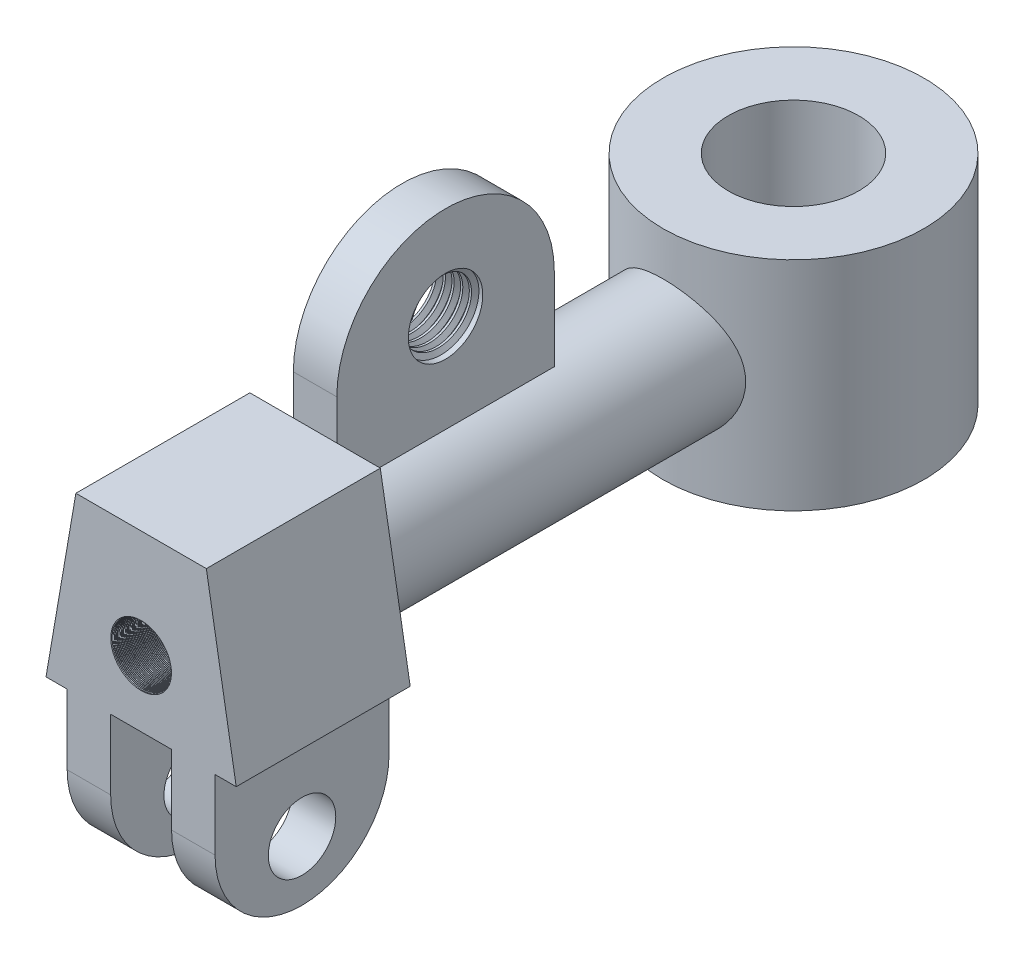
SolidWorks part; units mm, degrees
ref_plane "Front Plane" through (0, 0, 0) normal (0, 0, 1) x (1, 0, 0)
ref_plane "Top Plane" through (0, 0, 0) normal (0, 1, 0) x (1, 0, 0)
ref_plane "Right Plane" through (0, 0, 0) normal (1, 0, 0) x (0, 0, -1)
sketch "Sketch1" plane through (0, 0, 0) normal (0, 1, 0) x (1, 0, 0)
  line L0 (0, 0) -> (0, 27608.447) construction
  line L1 (0, 0) -> (-27608.447, 0) construction
  circle A0 centre (0, 0) radius 15
  circle A1 centre (0, 0) radius 30
  dimension "D1" = 30
  dimension "D2" = 60
extrude "Boss-Extrude1" add sketch "Sketch1" along normal mid plane 50
ref_plane "Plane1" through (0, 0, 130) normal (0, 0, 1) x (1, 0, 0)
sketch "Sketch2" plane through (0, 0, 130) normal (0, 0, 1) x (1, 0, 0)
  line L0 (-21.868, -15.1886) -> (21.868, -15.1886)
  line L1 (21.868, -15.1886) -> (15, 24.8114)
  line L2 (15, 24.8114) -> (-15, 24.8114)
  line L3 (-15, 24.8114) -> (-21.868, -15.1886)
  circle A0 centre (0, 0) radius 6.9775
  point P5 (0, 24.8114)
  point P8 (0, 0)
  point P9 (0, -15.1886)
  point P10 (0, 0)
  point P11 (0, 0)
  point P12 (0, 0)
  dimension "D1" = 43.736
  dimension "D2" = 40
  dimension "D3" = 30
extrude "Boss-Extrude2" add sketch "Sketch2" against normal blind 20 and the other way blind 20 separate body
sketch "Sketch3" plane through (0, 0, 110) normal (0, 0, -1) x (-1, 0, 0)
  circle A0 centre (0, 0) radius 6.9775 construction
  circle A1 centre (0, 0) radius 6.9775
  circle A2 centre (0, 0) radius 15
  dimension " 30" = 30
extrude "Boss-Extrude3" add sketch "Sketch3" along normal up to next
ref_plane "Plane2" through (22, 0, 0) normal (1, 0, 0) x (0, 0, -1)
sketch "Sketch8" plane through (22, 0, 0) normal (1, 0, 0) x (0, 0, -1)
  line L0 (-150, -15.1886) -> (-150, -51.2498)
  line L1 (-150, -51.2498) -> (-110, -51.2498)
  line L2 (-110, -51.2498) -> (-110, -15.1886)
  line L3 (-110, -15.1886) -> (-150, -15.1886)
extrude "Boss-Extrude4" add sketch "Sketch8" against normal blind 10 from offset 5 offset against normal yes
sketch "Sketch9" plane through (17, 0, 0) normal (1, 0, 0) x (0, 0, -1)
  circle A0 centre (-130, -37.4946) radius 7.7568
extrude "Cut-Extrude1" cut sketch "Sketch9" against normal blind 10
fillet "Fillet1" 2 edges at (12, -51.2498, 150) (12, -51.2498, 110) type full round first side face at (6, -14.2039, 150) second side face at (-15, 0, 110) middle face at (12, -51.2498, 130)
mirror "Mirror1" about plane through (0, 0, 0) normal (1, 0, 0) of "Cut-Extrude1", "Boss-Extrude4", "Fillet1"
ref_plane "Plane3" through (0, 15, 0) normal (0, 1, 0) x (1, 0, 0)
sketch "Sketch10" plane through (0, 15, 0) normal (0, 1, 0) x (1, 0, 0)
  line L0 (-5, -60) -> (-5, -110)
  line L1 (-5, -110) -> (5, -110)
  line L2 (5, -110) -> (5, -60)
  line L3 (5, -60) -> (-5, -60)
  line L4 (15, -110) -> (-15, -110) construction
  point P7 (0, -60)
  dimension "D1" = 10
  dimension "D2" = 50
extrude "Boss-Extrude7" add sketch "Sketch10" along normal blind 44 separate body
sketch "Sketch11" plane through (5, 0, 0) normal (1, 0, 0) x (0, 0, -1)
  line L0 (-110, 59) -> (-60, 59) construction
  circle A0 centre (-85, 37.5599) radius 8.5566
  point P2 (0, 0)
  point P5 (-85, 59)
extrude "Cut-Extrude2" cut sketch "Sketch11" against normal blind 44
fillet "Fillet2" 2 edges at (0, 59, 110) (0, 59, 60) type full round first side face at (0, 37, 110) second side face at (0, 37, 60) middle face at (0, 59, 85)
sketch3d "3DSketch1"
  circle A0 centre (0, 0, 150) radius 6.9775 construction
  circle A1 centre (0, 0, 150) radius 6.9775
  point P2 (0, 0, 156.9775)
  point P4 (0, 0, 156.9775)
thread "Thread1" pitch 0.3175 method extrude profile "Thread Profile2" start angle 20, offset 0, length 10, pitch 0.3175, diameter 13.955
ref_plane "Plane5" through (-6.5567, 2.3864, 150) normal (-0.342, -0.9397, 0) x (-0.9397, 0.342, 0)
sketch "Thread Profile2" plane through (-6.5567, 2.3864, 150) normal (-0.342, -0.9397, 0) x (-0.9397, 0.342, 0)
  line L0 (0, 0) -> (0, 0.3175) construction
  line L11 (0, 0) -> (0, 0.2778)
  line L12 (0, 0.2778) -> (-0.1719, 0.1786)
  line L13 (-0.1719, 0.1786) -> (-0.1719, 0.0992)
  line L15 (-0.1719, 0.0992) -> (0, 0)
  line L17 (-0.1719, 0.1389) -> (0, 0.1389) construction
  point P2 (0, 0)
  dimension "Pitch" = 0.3175
  dimension "Profile_Angle" = 60
  dimension "Profile_Land" = 0.0794
  dimension "Profile_Height" = 0.1719
thread "Thread2" pitch 2 method extrude profile "Thread Profile3" start angle 20, offset 0, length 10, pitch 2, diameter 17.1131
ref_plane "Plane6" through (5, 40.4864, 93.0405) normal (0, -0.9397, 0.342) x (0, 0.342, 0.9397)
sketch "Thread Profile3" plane through (5, 40.4864, 93.0405) normal (0, -0.9397, 0.342) x (0, 0.342, 0.9397)
  line L0 (0, 0) -> (0, 2) construction
  line L11 (0, 0) -> (0, 1.75)
  line L12 (0, 1.75) -> (-1.0825, 1.125)
  line L13 (-1.0825, 1.125) -> (-1.0825, 0.625)
  line L15 (-1.0825, 0.625) -> (0, 0)
  line L17 (-1.0825, 0.875) -> (0, 0.875) construction
  point P2 (0, 0)
  dimension "Pitch" = 2
  dimension "Profile_Angle" = 60
  dimension "Profile_Land" = 0.5
  dimension "Profile_Height" = 1.0825
